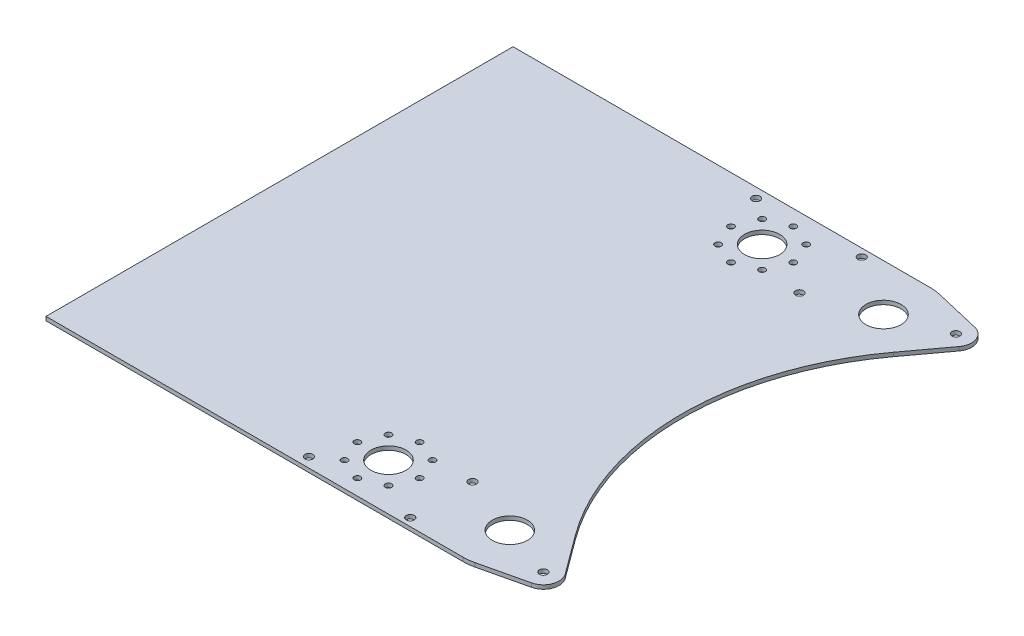
SolidWorks part; units mm, degrees
material "6061-T6 (SS)"
ref_plane "Front Plane" through (0, 0, 0) normal (0, 0, 1) x (1, 0, 0)
ref_plane "Top Plane" through (0, 0, 0) normal (0, 1, 0) x (1, 0, 0)
ref_plane "Right Plane" through (0, 0, 0) normal (1, 0, 0) x (0, 0, -1)
sketch "Sketch1" plane through (0, 0, 0) normal (0, 1, 0) x (1, 0, 0)
  line L1 (215.9, -190.5) -> (-215.9, -190.5)
  line L2 (215.9, -190.5) -> (215.9, 190.5)
  line L3 (215.9, 190.5) -> (-215.9, 190.5)
  line L4 (-215.9, -190.5) -> (-215.9, 190.5)
  line L5 (215.9, -190.5) -> (-215.9, 190.5) construction
  line L6 (215.9, 190.5) -> (-215.9, -190.5) construction
  point P0 (0, 0)
  dimension "D1" = 431.8
  dimension "D2" = 381
extrude "Boss-Extrude1" add sketch "Sketch1" along normal blind 3.175
sketch "Sketch6" plane through (0, 3.175, 0) normal (0, 1, 0) x (1, 0, 0)
  line L1 (25.4, 152.4) -> (0, 0) construction
  line L2 (0, 0) -> (25.4, -152.4) construction
  line L5 (-215.9, 190.5) -> (-215.9, -190.5) construction
  circle A0 centre (25.4, -152.4) radius 38.1 construction
  circle A1 centre (25.4, 152.4) radius 38.1 construction
  circle A2 centre (124.4092, -152.4) radius 38.1 construction
  circle A3 centre (124.4092, 152.4) radius 38.1 construction
  dimension "D1" = 76.2
  dimension "D5" = 228.6
  dimension "D3" = 99.0092
  dimension "D4" = 241.3
sketch "Sketch7" plane through (0, 3.175, 0) normal (0, 1, 0) x (1, 0, 0)
  circle A0 centre (124.4092, -152.4) radius 14.3129
  circle A1 centre (124.4092, 152.4) radius 14.3129
  circle A2 centre (25.4, 152.4) radius 14.3129
  circle A3 centre (25.4, -152.4) radius 14.3129
  circle A4 centre (0, 152.4) radius 2.5527
  circle A5 centre (25.4, 152.4) radius 25.4 construction
  circle A6 centre (7.4395, 170.3605) radius 2.5527
  circle A7 centre (25.4, 177.8) radius 2.5527
  circle A8 centre (43.3605, 170.3605) radius 2.5527
  circle A9 centre (25.4, -152.4) radius 25.4 construction
  circle A10 centre (25.4, -127) radius 2.5527
  circle A11 centre (43.3605, -134.4395) radius 2.5527
  circle A12 centre (50.8, -152.4) radius 2.5527
  circle A13 centre (43.3605, -170.3605) radius 2.5527
  circle A14 centre (50.8, 152.4) radius 2.5527
  circle A15 centre (43.3605, 134.4395) radius 2.5527
  circle A16 centre (25.4, 127) radius 2.5527
  circle A17 centre (7.4395, 134.4395) radius 2.5527
  circle A18 centre (25.4, -177.8) radius 2.5527
  circle A19 centre (7.4395, -170.3605) radius 2.5527
  circle A20 centre (0, -152.4) radius 2.5527
  circle A21 centre (7.4395, -134.4395) radius 2.5527
  point P24 (25.4, 152.4)
  point P34 (25.4, -152.4)
  dimension "D1" = 28.6258
  dimension "D2" = 28.6258
  dimension "D3" = 5.1054
  dimension "D5" = 50.8
  dimension "D4" = 8
  dimension "D6" = 8
extrude "Axle Holes" cut sketch "Sketch7" against normal through all
sketch "Sketch10" plane through (0, 3.175, 0) normal (0, 1, 0) x (1, 0, 0)
  line L0 (0, 0) -> (57.9248, 0) construction
  circle A0 centre (-9.525, -182.3949) radius 3.2385
  circle A1 centre (74.9046, -184.15) radius 3.2385
  circle A2 centre (74.9046, -133.35) radius 2.5527 construction
  circle A3 centre (74.9046, -133.35) radius 3.2385
  circle A4 centre (167.623, -168.275) radius 3.2385
  circle A10 centre (-9.525, -182.3949) radius 2.5527 construction
  circle A11 centre (74.9046, -184.15) radius 2.5527 construction
  circle A12 centre (167.623, -168.275) radius 2.5527 construction
  circle A13 centre (74.9046, -133.35) radius 2.5527 construction
  circle A14 centre (-9.525, -182.3949) radius 2.5527 construction
  circle A15 centre (74.9046, -184.15) radius 2.5527 construction
  circle A16 centre (167.623, -168.275) radius 2.5527 construction
  circle A17 centre (167.623, 168.275) radius 3.2385
  circle A18 centre (74.9046, 184.15) radius 3.2385
  circle A19 centre (74.9046, 133.35) radius 3.2385
  circle A20 centre (-9.525, 182.3949) radius 3.2385
  dimension "D1" = 6.477
extrude "Cut-Extrude5" cut sketch "Sketch10" against normal through all
sketch "Sketch8" plane through (0, 3.175, 0) normal (0, 1, 0) x (1, 0, 0)
  line L0 (155.0606, -129.7704) -> (177.8913, -160.6941)
  line L1 (133.1219, -189.4904) -> (170.5418, -180.7003)
  line L5 (0, 0) -> (-35.0112, 0) construction
  line L6 (155.0606, 129.7704) -> (177.8913, 160.6941)
  line L7 (133.1219, 189.4904) -> (170.5418, 180.7003)
  circle A4 centre (124.4092, -152.4) radius 38.1 construction
  circle A5 centre (167.623, -168.275) radius 12.7635 construction
  arc A7 (170.5418, -180.7003) -> (177.8913, -160.6941) centre (167.623, -168.275) ccw
  arc A8 (155.0606, -129.7704) -> (155.0606, 129.7704) centre (330.8323, 0) cw
  circle A9 centre (167.623, -168.275) radius 3.2385 construction
  arc A10 (170.5418, 180.7003) -> (177.8913, 160.6941) centre (167.623, 168.275) cw
  arc A11 (133.1219, -189.4904) -> (124.4092, -190.5) centre (124.4092, -152.4) cw
  arc A12 (133.1219, 189.4904) -> (124.4092, 190.5) centre (124.4092, 152.4) ccw
  dimension "D2" = 9.525
  dimension "D1" = 76.2
extrude "Cut-Extrude4" cut sketch "Sketch8" against normal through all flip side to cut
